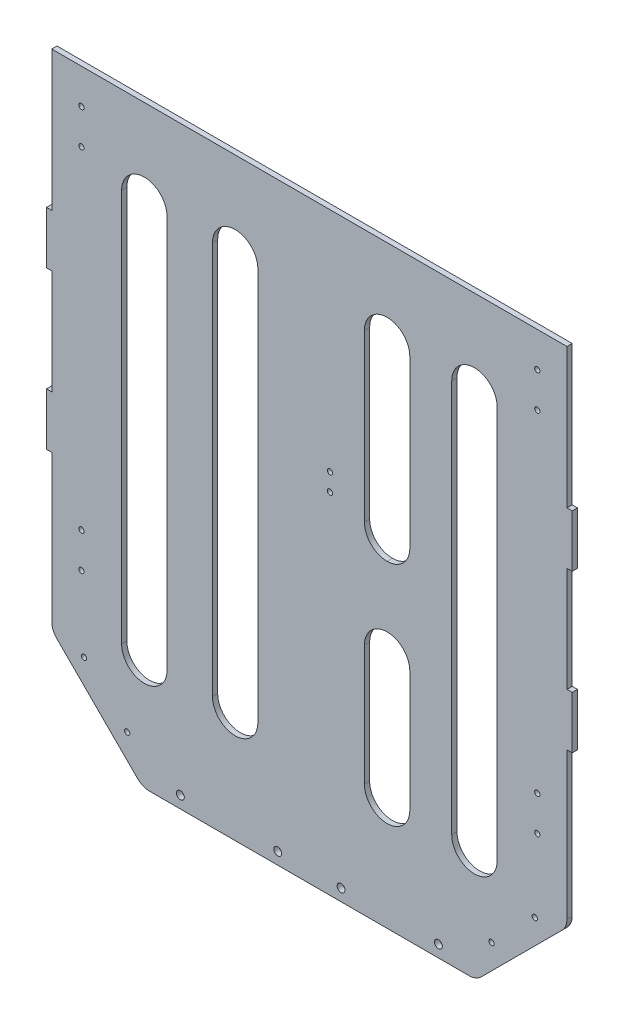
SolidWorks part; units mm, degrees
ref_plane "前视基准面" through (0, 0, 0) normal (0, 0, 1) x (1, 0, 0)
ref_plane "上视基准面" through (0, 0, 0) normal (0, 1, 0) x (1, 0, 0)
ref_plane "右视基准面" through (0, 0, 0) normal (1, 0, 0) x (0, 0, -1)
sketch "草图1" plane through (0, 0, 0) normal (0, 0, 1) x (1, 0, 0)
  line L0 (-147.5, 90) -> (-150.5, 90)
  line L1 (-147.5, 170) -> (147.5, 170)
  line L2 (-147.5, 170) -> (-147.5, 90)
  line L3 (-147.5, -170) -> (147.5, -170)
  line L4 (147.5, 170) -> (147.5, 90)
  line L5 (-147.5, 170) -> (147.5, -170) construction
  line L6 (-147.5, -170) -> (147.5, 170) construction
  line L7 (-150.5, 90) -> (-150.5, 60)
  line L8 (-150.5, 60) -> (-147.5, 60)
  line L9 (-147.5, 60) -> (-147.5, 0)
  line L10 (-147.5, 0) -> (-150.5, 0)
  line L11 (-150.5, 0) -> (-150.5, -30)
  line L12 (-150.5, -30) -> (-147.5, -30)
  line L13 (-147.5, -90) -> (-150.5, -90) construction
  line L14 (-150.5, -90) -> (-150.5, -120) construction
  line L15 (-150.5, -120) -> (-147.5, -120) construction
  line L16 (-147.5, -30) -> (-147.5, -90)
  line L17 (-147.5, -120) -> (-147.5, -170)
  line L18 (0, 0) -> (0, 121.9272) construction
  line L19 (147.5, -90) -> (150.5, -90) construction
  line L20 (150.5, -90) -> (150.5, -120) construction
  line L21 (150.5, -120) -> (147.5, -120) construction
  line L22 (147.5, 0) -> (150.5, 0)
  line L23 (150.5, 0) -> (150.5, -30)
  line L24 (150.5, -30) -> (147.5, -30)
  line L25 (147.5, 90) -> (150.5, 90)
  line L26 (150.5, 90) -> (150.5, 60)
  line L27 (150.5, 60) -> (147.5, 60)
  line L28 (147.5, -120) -> (147.5, -170)
  line L29 (147.5, -30) -> (147.5, -90)
  line L30 (147.5, 60) -> (147.5, 0)
  line L31 (-147.5, -90) -> (-147.5, -120)
  line L32 (147.5, -90) -> (147.5, -120)
  point P0 (0, 0)
  dimension "D1" = 295
  dimension "D2" = 340
  dimension "D3" = 30
  dimension "D4" = 3
  dimension "D5" = 80
  dimension "D6" = 3
  dimension "D7" = 30
  dimension "D8" = 30
  dimension "D9" = 3
  dimension "D10" = 50
  dimension "D11" = 60
extrude "凸台-拉伸1" add sketch "草图1" along normal blind 3
sketch "草图3" plane through (0, 0, 3) normal (0, 0, 1) x (1, 0, 0)
  line L0 (-147.5, -118) -> (-95.5, -170)
  line L1 (-147.5, -30) -> (-147.5, -170) construction
  line L2 (-147.5, -170) -> (147.5, -170) construction
  line L3 (-95.5, -170) -> (-147.5, -170)
  line L4 (-147.5, -170) -> (-147.5, -118)
  line L5 (147.5, -170) -> (147.5, -118)
  line L6 (147.5, -170) -> (147.5, -30) construction
  line L7 (147.5, -118) -> (95.5, -170)
  line L8 (95.5, -170) -> (147.5, -170)
  dimension "D1" = 52
  dimension "D2" = 52
  dimension "D3" = 52
  dimension "D4" = 52
extrude "切除-拉伸2" cut sketch "草图3" against normal through all
fillet "圆角1" [suppressed] radius 5
sketch "草图2" plane through (0, 0, 3) normal (0, 0, 1) x (1, 0, 0)
  line L0 (-95.5, -170) -> (95.5, -170) construction
  line L1 (0, -170) -> (0, -88.9982) construction
  circle A2 centre (73.85, -163.15) radius 2.25 construction
  circle A3 centre (18.15, -163.15) radius 2.25 construction
  circle A4 centre (-73.85, -163.15) radius 2.25 construction
  circle A5 centre (-18.15, -163.15) radius 2.25 construction
  circle A6 centre (11.8005, 40) radius 1.5
  circle A7 centre (11.8005, 30) radius 1.5
  circle A8 centre (73.85, -163.15) radius 2.25 construction
  circle A9 centre (18.15, -163.15) radius 2.25 construction
  circle A10 centre (-73.85, -163.15) radius 2.25 construction
  circle A11 centre (-18.15, -163.15) radius 2.25 construction
  circle A12 centre (-73.85, -163.15) radius 2.25
  circle A13 centre (-18.15, -163.15) radius 2.25
  circle A14 centre (18.15, -163.15) radius 2.25
  circle A15 centre (73.85, -163.15) radius 2.25
  dimension "D1" = 4.5
  dimension "D2" = 4.5
  dimension "D5" = 3
  dimension "D6" = 3
  dimension "D3" = 55.7
  dimension "D4" = 18.15
extrude "切除-拉伸1" cut sketch "草图2" against normal blind 10
sketch "草图4" plane through (0, 0, 3) normal (0, 0, 1) x (1, 0, 0)
  line L0 (147.5, 170) -> (-147.5, 170) construction
  line L1 (147.5, 90) -> (147.5, 170) construction
  line L2 (147.5, -118) -> (147.5, -30) construction
  line L3 (0, 170) -> (0, 113.7599) construction
  circle A0 centre (130.5, 150) radius 1.5
  circle A1 centre (130.5, 130) radius 1.5
  circle A2 centre (130.5, -60) radius 1.5
  circle A3 centre (130.5, -80) radius 1.5
  circle A4 centre (-130.5, -80) radius 1.5
  circle A5 centre (-130.5, -60) radius 1.5
  circle A6 centre (-130.5, 130) radius 1.5
  circle A7 centre (-130.5, 150) radius 1.5
  dimension "D1" = 20
  dimension "D2" = 20
  dimension "D3" = 190
  dimension "D4" = 20
  dimension "D5" = 17
  dimension "D6" = 17
  dimension "D7" = 17
  dimension "D8" = 17
  dimension "D9" = 3
  dimension "D10" = 3
  dimension "D11" = 3
  dimension "D12" = 3
extrude "切除-拉伸3" cut sketch "草图4" against normal through all
sketch "草图5" plane through (0, 0, 3) normal (0, 0, 1) x (1, 0, 0)
  line L0 (-94.5, 120) -> (-94.5, -105) construction
  line L1 (-81.5, 120) -> (-81.5, -105)
  line L2 (-107.5, 120) -> (-107.5, -105)
  line L3 (147.5, 170) -> (-147.5, 170) construction
  line L4 (-147.5, 60) -> (-147.5, 0) construction
  line L5 (-42.5, 120) -> (-42.5, -105) construction
  line L6 (-29.5, 120) -> (-29.5, -105)
  line L7 (-55.5, 120) -> (-55.5, -105)
  line L8 (44.5, 120) -> (44.5, -105) construction
  line L9 (57.5, 120) -> (57.5, -105)
  line L10 (31.5, 120) -> (31.5, -105)
  line L11 (94.5, 120) -> (94.5, -105) construction
  line L12 (107.5, 120) -> (107.5, -105)
  line L13 (81.5, 120) -> (81.5, -105)
  arc A0 (-81.5, 120) -> (-107.5, 120) centre (-94.5, 120) ccw
  arc A1 (-107.5, -105) -> (-81.5, -105) centre (-94.5, -105) ccw
  arc A2 (-29.5, 120) -> (-55.5, 120) centre (-42.5, 120) ccw
  arc A3 (-55.5, -105) -> (-29.5, -105) centre (-42.5, -105) ccw
  arc A4 (57.5, 120) -> (31.5, 120) centre (44.5, 120) ccw
  arc A5 (31.5, -105) -> (57.5, -105) centre (44.5, -105) ccw
  arc A6 (107.5, 120) -> (81.5, 120) centre (94.5, 120) ccw
  arc A7 (81.5, -105) -> (107.5, -105) centre (94.5, -105) ccw
  point P2 (-94.5, 7.5)
  point P14 (-42.5, 7.5)
  point P22 (44.5, 7.5)
  point P29 (94.5, 7.5)
  dimension "D1" = 13
  dimension "D2" = 225
  dimension "D3" = 50
  dimension "D4" = 53
  dimension "D8" = 52
  dimension "D9" = 87
  dimension "D5" = 2
  dimension "D6" = 2
  dimension "D7" = 2
extrude "切除-拉伸4" cut sketch "草图5" against normal through all
sketch "草图6" plane through (0, 0, 3) normal (0, 0, 1) x (1, 0, 0)
  line L0 (31.5, 120) -> (31.5, -105) construction
  line L1 (31.5, 12) -> (57.5, 12)
  line L2 (31.5, 12) -> (31.5, -23)
  line L3 (31.5, -23) -> (57.5, -23)
  line L4 (57.5, 12) -> (57.5, -23)
  line L5 (57.5, -105) -> (57.5, 120) construction
  arc A0 (57.5, 120) -> (31.5, 120) centre (44.5, 120) ccw construction
  dimension "D1" = 35
  dimension "D2" = 108
extrude "凸台-拉伸2" add sketch "草图6" against normal up to surface (3 mm away) up to face at (-42.5, 7.5, 0)
fillet "圆角2" radius 13 4 edges at (57.5, -23, 1.5) (31.5, -23, 1.5) (57.5, 12, 1.5) (31.5, 12, 1.5)
sketch "草图7" plane through (0, 0, 3) normal (0, 0, 1) x (1, 0, 0)
  line L0 (0.5, 120) -> (0.5, 35) construction
  line L1 (10.5, 120) -> (10.5, 35)
  line L2 (-9.5, 120) -> (-9.5, 35)
  line L3 (31.5, 120) -> (31.5, 25) construction
  arc A0 (10.5, 120) -> (-9.5, 120) centre (0.5, 120) ccw
  arc A1 (-9.5, 35) -> (10.5, 35) centre (0.5, 35) ccw
  point P2 (0.5, 77.5)
  point P7 (0, 0)
  point P9 (0, 0)
  point P10 (3.5, 118.5256)
  point P12 (3.5, 123.7542)
  point P15 (3.5, 35.6141)
  dimension "D1" = 10
  dimension "D2" = 21
  dimension "D3" = 85
fillet "圆角3" radius 10 4 edges at (147.5, -118, 1.5) (95.5, -170, 1.5) (-95.5, -170, 1.5) (-147.5, -118, 1.5)
sketch "草图8" plane through (0, 0, 3) normal (0, 0, 1) x (1, 0, 0)
  line L0 (-129.0441, -122.3138) -> (-104.2954, -147.0625) construction
  line L1 (-98.4289, -167.0711) -> (-144.5711, -120.9289) construction
  line L2 (-147.5, -99.7493) -> (147.5, -99.7493) construction
  line L3 (-147.5, -30) -> (-147.5, -113.8579) construction
  line L4 (147.5, -113.8579) -> (147.5, -30) construction
  line L5 (0, -99.7493) -> (0, -54.3911) construction
  line L6 (129.0441, -122.3138) -> (104.2954, -147.0625) construction
  circle A0 centre (-129.0441, -122.3138) radius 1.5
  circle A1 centre (-104.2954, -147.0625) radius 1.5
  circle A2 centre (104.2954, -147.0625) radius 1.5
  circle A3 centre (129.0441, -122.3138) radius 1.5
  dimension "D1" = 3
  dimension "D2" = 3
  dimension "D3" = 10
  dimension "D4" = 35
extrude "切除-拉伸5" cut sketch "草图8" against normal through all
